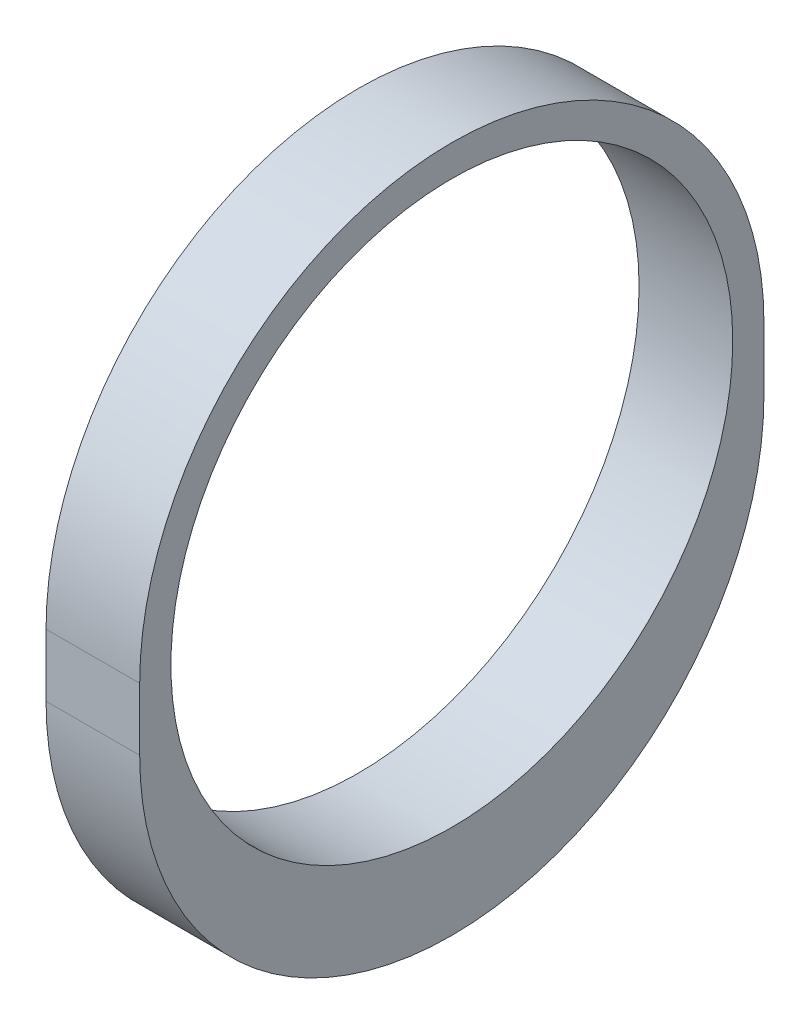
SolidWorks part; units mm, degrees
ref_plane "Piano frontale" through (0, 0, 0) normal (0, 0, 1) x (1, 0, 0)
ref_plane "Piano superiore" through (0, 0, 0) normal (0, 1, 0) x (1, 0, 0)
ref_plane "Piano destro" through (0, 0, 0) normal (1, 0, 0) x (0, 0, -1)
sketch "Schizzo1" plane through (0, 0, 0) normal (1, 0, 0) x (0, 0, -1)
  line L0 (0, -12) -> (0, 10) construction
  line L1 (-10, 0) -> (10, 0) construction
  line L2 (-10, 0) -> (-10, -2)
  line L3 (10, 0) -> (10, -2)
  circle A0 centre (0, 0) radius 9
  arc A1 (10, 0) -> (-10, 0) centre (0, 0) ccw
  arc A2 (-10, -2) -> (10, -2) centre (0, -2) ccw
  point P7 (0, 0)
  point P10 (0, 0)
  dimension "D1" = 18
  dimension "D2" = 10
  dimension "D4" = 10
  dimension "D3" = 2
extrude "Estrusione-Estrusione1" add sketch "Schizzo1" along normal mid plane 3
